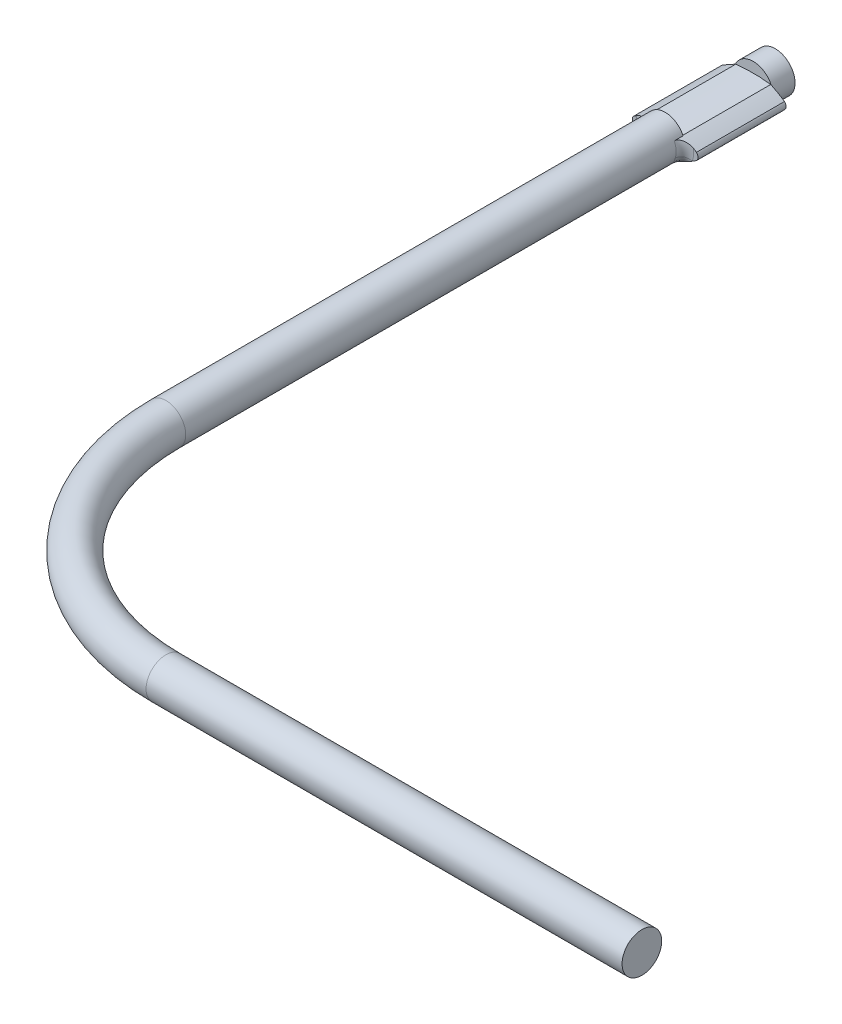
SolidWorks part; units mm, degrees
ref_plane "Front Plane" through (0, 0, 0) normal (0, 0, 1) x (1, 0, 0)
ref_plane "Top Plane" through (0, 0, 0) normal (0, 1, 0) x (1, 0, 0)
ref_plane "Right Plane" through (0, 0, 0) normal (1, 0, 0) x (0, 0, -1)
sketch "Sketch1" plane through (0, 0, 0) normal (0, 0, 1) x (1, 0, 0)
  circle A0 centre (0, 0) radius 2.286
  dimension "D1" = 4.572
sketch3d "3DSketch2"
  line L0 (0, 0, 0) -> (0, 0, 70.2775)
  line L1 (25.4, 0, 95.6775) -> (80.2978, 0, 95.6775)
  arc A0 (0, 0, 70.2775) -> (25.4, 0, 95.6775) centre (25.4, 0, 70.2775) ccw
  point P6 (0, 0, 95.6775)
  point P7 (25.4, 25.4, 70.2775)
  dimension "D1" = 25.4
sweep "Sweep1" add profiles "Sketch1" path "3DSketch2"
ref_plane "Plane1" through (0, 0, 12.7) normal (0, 0, 1) x (1, 0, 0)
sketch "Sketch3" plane through (0, 0, 12.7) normal (0, 0, 1) x (1, 0, 0)
  line L0 (3.825, -1.0589) -> (3.6162, -0.7402)
  line L1 (3.6162, 0.0906) -> (3.825, 0.4093)
  line L2 (-3.6162, -0.7402) -> (-3.825, -1.0589)
  line L3 (-3.825, 0.4093) -> (-3.6162, 0.0906)
  line L4 (0, 3.3429) -> (0, -4.023) construction
  circle A0 centre (0, 0) radius 2.286
  arc A1 (-0.8972, -2.1223) -> (0.8972, -2.1223) centre (0, 0.254) ccw
  arc A2 (-1.0317, -2.4787) -> (1.0317, -2.4787) centre (0, 0.254) ccw
  arc A3 (-3.6162, 0.0906) -> (-3.6162, -0.7402) centre (-3.2008, -0.3248) ccw
  arc A4 (3.6162, 0.0906) -> (3.6162, -0.7402) centre (3.2008, -0.3248) cw
  parabola Q0 (-2.0229, 0.9907) -> (2.0229, 0.9907) focus (0, -7.1981) apex (0, 1.1138)
  spline S0 degree 3 poles (3.6162, -0.7402) (3.3878, -0.8899) (2.5196, -1.4229) (1.5987, -1.8574) (0.8972, -2.1223) knots 0.154249 0.154249 0.154249 0.154249 0.327775 0.801446 0.801446 0.801446 0.801446
  spline S1 degree 3 poles (1.0317, -2.4787) (2.0114, -2.1088) (2.9491, -1.6329) (3.825, -1.0589) knots 0 0 0 0 1 1 1 1
  spline S2 degree 3 poles (3.825, 0.4093) (3.2826, 0.7647) (2.7165, 1.0829) (2.1309, 1.3614) knots 0 0 0 0 1 1 1 1
  spline S3 degree 3 poles (2.0229, 0.9907) (2.3272, 0.8444) (2.867, 0.56) (3.3878, 0.2403) (3.6162, 0.0906) knots 0.154249 0.154249 0.154249 0.154249 0.368987 0.542512 0.542512 0.542512 0.542512
  spline S4 degree 3 poles (2.1309, 1.3614) (1.7773, 1.4044) (1.4226, 1.439) (0.7123, 1.4836) (0.3566, 1.4948) (-0.3559, 1.4948) (-0.7118, 1.4836) (-1.4229, 1.439) (-1.7773, 1.4044) (-2.1309, 1.3614) knots 0 0 0 0 0.25 0.25 0.5 0.5 0.75 0.75 1 1 1 1
  spline S5 degree 3 poles (-3.825, -1.0589) (-2.9491, -1.6329) (-2.0114, -2.1088) (-1.0317, -2.4787) knots 0 0 0 0 1 1 1 1
  spline S6 degree 3 poles (-0.8972, -2.1223) (-1.5987, -1.8574) (-2.5196, -1.4229) (-3.3878, -0.8899) (-3.6162, -0.7402) knots 0.154249 0.154249 0.154249 0.154249 0.62792 0.801446 0.801446 0.801446 0.801446
  spline S7 degree 3 poles (-3.6162, 0.0906) (-3.3878, 0.2403) (-2.867, 0.56) (-2.3272, 0.8444) (-2.0229, 0.9907) knots 0.413183 0.413183 0.413183 0.413183 0.586708 0.801446 0.801446 0.801446 0.801446
  spline S8 degree 3 poles (-2.1309, 1.3614) (-2.7165, 1.0829) (-3.2826, 0.7647) (-3.825, 0.4093) knots 0 0 0 0 1 1 1 1
extrude "Boss-Extrude1" add sketch "Sketch3" against normal offset from surface (10.16 mm away) 2.54 contours S3 A0 A1 S0 A4 | S7 A3 S6 A1 A0 region at (2.7186, -0.4706, 12.7) region at (-2.7186, -0.4706, 12.7) up to face at (2.286, 0, 0)
sketch "Sketch4" plane through (0, 0, 12.7) normal (0, 0, 1) x (1, 0, 0)
  line L0 (3.825, -1.0589) -> (3.6162, -0.7402)
  line L1 (3.6162, 0.0906) -> (3.825, 0.4093)
  line L2 (-3.6162, -0.7402) -> (-3.825, -1.0589)
  line L3 (-3.825, 0.4093) -> (-3.6162, 0.0906)
  line L4 (0, 3.3429) -> (0, -4.023) construction
  circle A0 centre (0, 0) radius 2.286
  arc A1 (-0.8972, -2.1223) -> (0.8972, -2.1223) centre (0, 0.254) ccw
  arc A2 (-1.0317, -2.4787) -> (1.0317, -2.4787) centre (0, 0.254) ccw
  arc A3 (-3.6162, 0.0906) -> (-3.6162, -0.7402) centre (-3.2008, -0.3248) ccw
  arc A4 (3.6162, 0.0906) -> (3.6162, -0.7402) centre (3.2008, -0.3248) cw
  parabola Q0 (-2.0229, 0.9907) -> (2.0229, 0.9907) focus (0, -7.1981) apex (0, 1.1138)
  spline S0 degree 3 poles (3.6162, -0.7402) (3.3878, -0.8899) (2.5196, -1.4229) (1.5987, -1.8574) (0.8972, -2.1223) knots 0.154249 0.154249 0.154249 0.154249 0.327775 0.801446 0.801446 0.801446 0.801446
  spline S1 degree 3 poles (1.0317, -2.4787) (2.0114, -2.1088) (2.9491, -1.6329) (3.825, -1.0589) knots 0 0 0 0 1 1 1 1
  spline S2 degree 3 poles (3.825, 0.4093) (3.2826, 0.7647) (2.7165, 1.0829) (2.1309, 1.3614) knots 0 0 0 0 1 1 1 1
  spline S3 degree 3 poles (2.0229, 0.9907) (2.3272, 0.8444) (2.867, 0.56) (3.3878, 0.2403) (3.6162, 0.0906) knots 0.154249 0.154249 0.154249 0.154249 0.368987 0.542512 0.542512 0.542512 0.542512
  spline S4 degree 3 poles (2.1309, 1.3614) (1.7773, 1.4044) (1.4226, 1.439) (0.7123, 1.4836) (0.3566, 1.4948) (-0.3559, 1.4948) (-0.7118, 1.4836) (-1.4229, 1.439) (-1.7773, 1.4044) (-2.1309, 1.3614) knots 0 0 0 0 0.25 0.25 0.5 0.5 0.75 0.75 1 1 1 1
  spline S5 degree 3 poles (-3.825, -1.0589) (-2.9491, -1.6329) (-2.0114, -2.1088) (-1.0317, -2.4787) knots 0 0 0 0 1 1 1 1
  spline S6 degree 3 poles (-0.8972, -2.1223) (-1.5987, -1.8574) (-2.5196, -1.4229) (-3.3878, -0.8899) (-3.6162, -0.7402) knots 0.154249 0.154249 0.154249 0.154249 0.62792 0.801446 0.801446 0.801446 0.801446
  spline S7 degree 3 poles (-3.6162, 0.0906) (-3.3878, 0.2403) (-2.867, 0.56) (-2.3272, 0.8444) (-2.0229, 0.9907) knots 0.413183 0.413183 0.413183 0.413183 0.586708 0.801446 0.801446 0.801446 0.801446
  spline S8 degree 3 poles (-2.1309, 1.3614) (-2.7165, 1.0829) (-3.2826, 0.7647) (-3.825, 0.4093) knots 0 0 0 0 1 1 1 1
extrude "Cut-Extrude1" cut sketch "Sketch4" against normal up to surface (10.16 mm away) contours L4 A0 S4 | A0 L4 S4 | L4 S4 A0 S7 Q0 | S4 L4 Q0 S3 A0 region at (0.9758, 1.2622, 12.7) region at (0.7026, 1.7975, 12.7) region at (-0.9758, 1.2622, 12.7) region at (-0.7026, 1.7975, 12.7) up to face at (-2.372, -0.714, 2.54)
fillet "Fillet1" radius 1.016 2 edges at (1.9284, -1.2277, 12.7) (-1.9284, -1.2277, 12.7)
